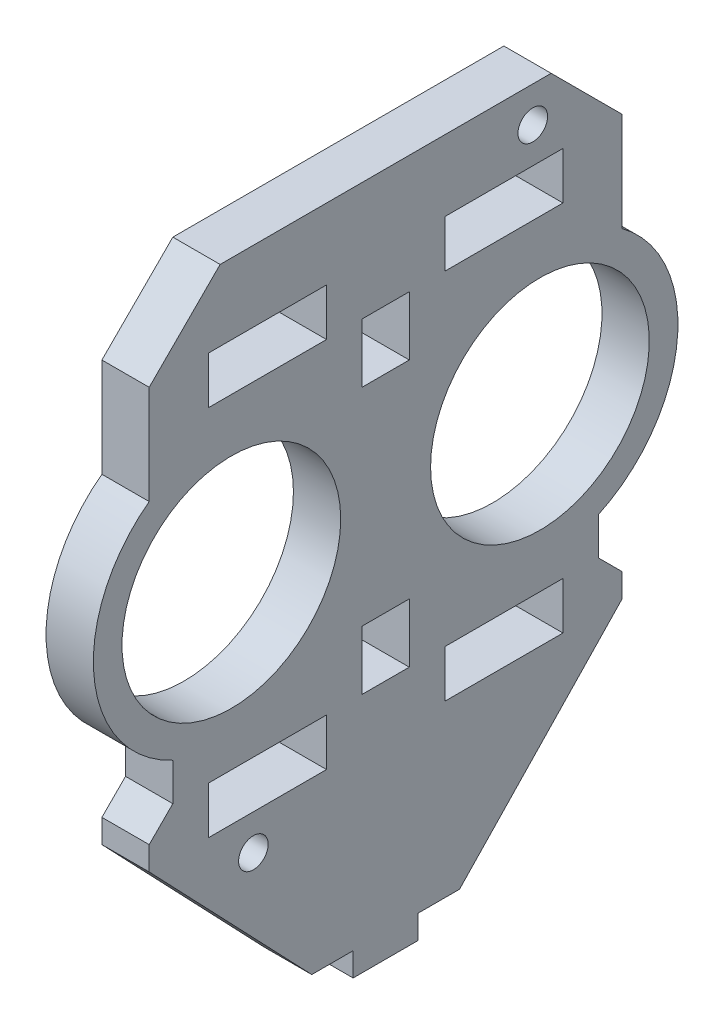
SolidWorks part; units mm, degrees
ref_plane "Front Plane" through (0, 0, 0) normal (0, 0, 1) x (1, 0, 0)
ref_plane "Top Plane" through (0, 0, 0) normal (0, 1, 0) x (1, 0, 0)
ref_plane "Right Plane" through (0, 0, 0) normal (1, 0, 0) x (0, 0, -1)
sketch "Sketch1" plane through (0, 0, 0) normal (1, 0, 0) x (0, 0, -1)
  line L0 (0, 86.3618) -> (0, -95.6447) construction
  line L1 (-34.45, 0) -> (67.35, 0) construction
  line L2 (-12.5, -64.29) -> (-40, -35.5)
  line L3 (-40, -31.5) -> (-40, -35.5)
  line L4 (-40, -31.5) -> (-36, -27.5)
  line L5 (-12.5, -64.29) -> (-12.5, -68.29)
  line L6 (-12.5, -68.29) -> (12.5, -68.29)
  line L7 (12.5, -64.29) -> (12.5, -68.29)
  line L8 (-36, -27.5) -> (-36, -21.1431)
  line L9 (-40, 35.5) -> (-40, 18.7571)
  line L10 (-40, 35.5) -> (-28, 47.5)
  line L11 (40, 35.5) -> (-40, 35.5) construction
  line L12 (40, 35.5) -> (40, 18.7571)
  line L13 (40, -35.5) -> (40, -31.5)
  line L14 (40, -31.5) -> (36, -27.5)
  line L15 (36, -27.5) -> (36, -21.1431)
  line L16 (12.5, -64.29) -> (40, -35.5)
  line L17 (40, -35.5) -> (30, -35.5) construction
  line L18 (40, 35.5) -> (28, 47.5)
  line L19 (-28, 47.5) -> (28, 47.5)
  line L22 (-40, -35.5) -> (-40, -27.5) construction
  line L24 (-30, -27.5) -> (-40, -27.5) construction
  circle A0 centre (0, 0) radius 76.29 construction
  circle A1 centre (-22.3739, -41.5) radius 2.5
  circle A2 centre (24.8916, 41.5) radius 2.5
  circle A3 centre (-26.1, 0) radius 23.3461 construction
  circle A4 centre (-26.1, 0) radius 18.5
  circle A5 centre (26.1, 0) radius 18.5
  circle A6 centre (26.1, 0) radius 23.3461 construction
  arc A9 (-40, 18.7571) -> (-36, -21.1431) centre (-26.1, 0) ccw
  arc A10 (40, 18.7571) -> (36, -21.1431) centre (26.1, 0) cw
  circle A11 centre (-26.1, 0) radius 8.35 construction
  circle A13 centre (70, 0) radius 2.65 construction
  circle A14 centre (-43.3013, -25) radius 7 construction
  point P14 (0, 0)
  point P16 (0, -76.29)
  point P20 (-62.4774, 0)
  point P27 (0, -68.29)
  point P30 (0, 56.7762)
  point P31 (0, 56.7762)
  dimension "D1" = 152.58
  dimension "D2" = 5
  dimension "D5" = 37
  dimension "D9" = 8
  dimension "D7" = 6
  dimension "D10" = 4
  dimension "D3" = 6
  dimension "D4" = 5
  dimension "D6" = 124.9548
  dimension "D8" = 25
  dimension "D11" = 12
  dimension "D12" = 12
  dimension "D15" = 4
extrude "Boss-Extrude1" add sketch "Sketch1" along normal blind 8
sketch "Sketch2" plane through (0, 0, 0) normal (-1, 0, 0) x (0, 0, 1)
  line L0 (0, -90.2636) -> (0, 91.611) construction
  line L1 (-93.4475, 0) -> (84.8595, 0) construction
  line L2 (10, -27.5) -> (10, -35.5)
  line L3 (-30, -27.5) -> (-10, -27.5)
  line L4 (-30, -27.5) -> (-30, -35.5)
  line L5 (-30, -35.5) -> (-10, -35.5)
  line L6 (-10, -27.5) -> (-10, -35.5)
  line L7 (30, -35.5) -> (10, -35.5)
  line L8 (30, -27.5) -> (30, -35.5)
  line L9 (30, -27.5) -> (10, -27.5)
  line L10 (30, 27.5) -> (10, 27.5)
  line L11 (30, 27.5) -> (30, 35.5)
  line L12 (30, 35.5) -> (10, 35.5)
  line L13 (-10, 27.5) -> (-10, 35.5)
  line L14 (-30, 35.5) -> (-10, 35.5)
  line L15 (-30, 27.5) -> (-30, 35.5)
  line L16 (-30, 27.5) -> (-10, 27.5)
  line L17 (10, 27.5) -> (10, 35.5)
  line L18 (4, 17.5) -> (4, 27.5)
  line L19 (-4, -17.5) -> (4, -17.5)
  line L20 (-4, -17.5) -> (-4, -27.5)
  line L21 (-4, -27.5) -> (4, -27.5)
  line L22 (4, -17.5) -> (4, -27.5)
  line L23 (-4, 27.5) -> (4, 27.5)
  line L24 (-4, 17.5) -> (-4, 27.5)
  line L25 (-4, 17.5) -> (4, 17.5)
  line L26 (5.5, -68.29) -> (5.5, -64.29)
  line L27 (-12.5, -68.29) -> (-5.5, -68.29)
  line L28 (-12.5, -68.29) -> (-12.5, -64.29)
  line L29 (-12.5, -64.29) -> (-5.5, -64.29)
  line L30 (-5.5, -68.29) -> (-5.5, -64.29)
  line L31 (12.5, -64.29) -> (5.5, -64.29)
  line L32 (12.5, -68.29) -> (12.5, -64.29)
  line L33 (12.5, -68.29) -> (5.5, -68.29)
  point P26 (0, -17.5)
  dimension "D1" = 27.5
  dimension "D2" = 20
  dimension "D3" = 20
  dimension "D4" = 8
  dimension "D5" = 8
  dimension "D6" = 10
  dimension "D7" = 4
  dimension "D8" = 7
extrude "Cut-Extrude1" cut sketch "Sketch2" against normal up to next
